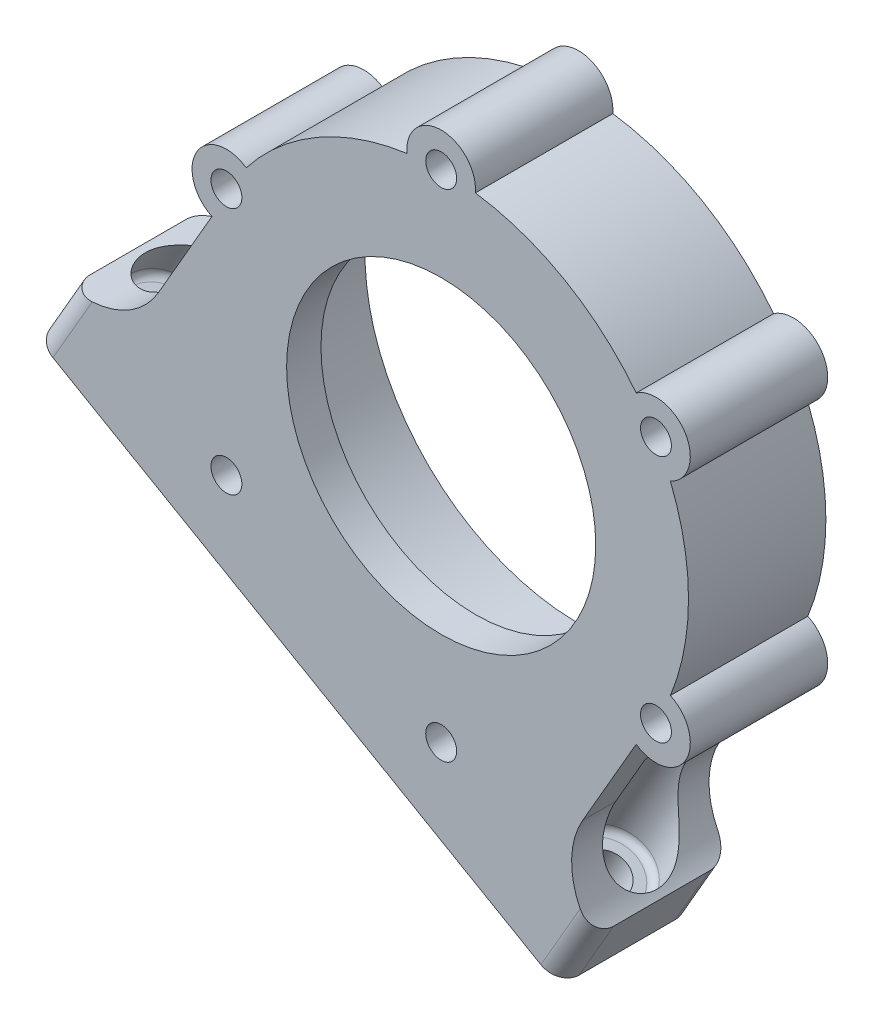
SolidWorks part; units mm, degrees
ref_plane "Front Plane" through (0, 0, 0) normal (0, 0, 1) x (1, 0, 0)
ref_plane "Top Plane" through (0, 0, 0) normal (0, 1, 0) x (1, 0, 0)
ref_plane "Right Plane" through (0, 0, 0) normal (1, 0, 0) x (0, 0, -1)
sketch "Sketch1" plane through (0, 0, 0) normal (0, 0, 1) x (1, 0, 0)
  circle A0 centre (0, 0) radius 31.1
  circle A1 centre (0, 0) radius 36
  dimension "D1" = 72
  dimension "D2" = 62.2
extrude "Boss-Extrude1" add sketch "Sketch1" along normal blind 15
sketch "Sketch2" plane through (0, 0, 15) normal (0, 0, 1) x (1, 0, 0)
  circle A0 centre (0, 0) radius 36
extrude "Boss-Extrude2" add sketch "Sketch2" along normal blind 5
sketch "Sketch3" plane through (0, 0, 20) normal (0, 0, 1) x (1, 0, 0)
  circle A0 centre (0, 0) radius 22.5
  dimension "D1" = 45
extrude "Cut-Extrude1" cut sketch "Sketch3" against normal blind 5
sketch "Sketch4" plane through (0, 0, 0) normal (0, 0, -1) x (-1, 0, 0)
  line L0 (0, 0) -> (0, 36) construction
  circle A0 centre (0, 0) radius 31.1 construction
  circle A1 centre (0, 36.1) radius 5
  circle A2 centre (31.2635, 18.05) radius 5
  circle A3 centre (31.2635, -18.05) radius 5
  circle A4 centre (0, -36.1) radius 5
  circle A5 centre (-31.2635, -18.05) radius 5
  circle A6 centre (-31.2635, 18.05) radius 5
  point P20 (0, 0)
  dimension "D1" = 10
  dimension "D2" = 6
extrude "Boss-Extrude3" add sketch "Sketch4" against normal up to surface (20 mm away) up to face at (22.5, 0, 20)
sketch "Sketch8" plane through (0, 0, 0) normal (0, 0, -1) x (-1, 0, 0)
  line L0 (-28.3871, -22.1398) -> (-9.8771, -54.2001)
  line L1 (-9.8771, -54.2001) -> (51.8772, -18.5462)
  line L2 (51.8772, -18.5462) -> (33.3672, 13.5141)
  line L3 (21, -36.3731) -> (0, 0) construction
  line L4 (-28.3871, -22.1398) -> (33.3672, 13.5141) construction
  arc A0 (-28.3871, -22.1398) -> (33.3672, 13.5141) centre (0, 0) ccw
  dimension "D1" = 37.02
extrude "Boss-Extrude4" add sketch "Sketch8" against normal blind 20
sketch "Sketch7" plane through (0, 0, 0) normal (0, 0, -1) x (-1, 0, 0)
  circle A0 centre (-31.2635, 18.05) radius 2.25
  circle A1 centre (0, 36.1) radius 2.25
  circle A2 centre (31.2635, 18.05) radius 2.25
  circle A3 centre (31.2635, -18.05) radius 2.25
  circle A4 centre (0, -36.1) radius 2.25
  circle A5 centre (-31.2635, -18.05) radius 2.25
  arc A6 (-28.3871, 22.1398) -> (-33.3672, 13.5141) centre (-31.2635, 18.05) ccw construction
  point P18 (0, 0)
  dimension "D1" = 4.5
  dimension "D2" = 6
extrude "Cut-Extrude2" cut sketch "Sketch7" against normal through all
sketch "Sketch9" plane through (-21, -36.3731, 0) normal (-0.5, -0.866, 0) x (0.866, -0.5, 0)
  line L0 (0, 0) -> (0, 15.6086) construction
  line L1 (-35.6539, 0) -> (-44.0039, 0)
  line L2 (-35.6539, 0) -> (-35.6539, 20)
  line L3 (-35.6539, 20) -> (-44.0039, 20)
  line L4 (-44.0039, 0) -> (-44.0039, 20)
  line L5 (35.6539, 0) -> (-35.6539, 0) construction
  line L6 (44.0039, 0) -> (44.0039, 20)
  line L7 (35.6539, 20) -> (44.0039, 20)
  line L8 (35.6539, 0) -> (35.6539, 20)
  line L9 (35.6539, 0) -> (44.0039, 0)
  dimension "D1" = 8.35
extrude "Boss-Extrude5" add sketch "Sketch9" against normal blind 10
fillet "Fillet1" radius 12 2 edges at (-46.8772, -9.8859, 10) (14.8771, -45.5398, 10)
sketch "Sketch10" plane through (-21, -36.3731, 0) normal (-0.5, -0.866, 0) x (0.866, -0.5, 0)
  line L0 (44.0039, 10) -> (0, 10) construction
  line L1 (44.0039, 0) -> (44.0039, 20) construction
  line L2 (0, 10) -> (0, 0) construction
  line L3 (44.0039, 0) -> (-44.0039, 0) construction
  circle A0 centre (37.5039, 10) radius 3
  circle A1 centre (-37.5039, 10) radius 3
  circle A2 centre (37.5039, 10) radius 5.5
  circle A3 centre (-37.5039, 10) radius 5.5
  dimension "D1" = 6
  dimension "D3" = 6.5
  dimension "D2" = 11
extrude "Cut-Extrude3" cut sketch "Sketch10" against normal blind 30 contours A0 | A1 region at (11.4793, -55.1251, 10) region at (-53.4793, -17.6212, 10)
extrude "Cut-Extrude5" cut sketch "Sketch10<4>" against normal blind 25 from offset 5 offset against normal yes
sketch "Sketch10<4>" plane through (-21, -36.3731, 0) normal (-0.5, -0.866, 0) x (0.866, -0.5, 0) same geometry as "Sketch10"
fillet "Fillet2" radius 3 4 edges at (-56.6085, -10.0411, 20) (-56.6085, -10.0411, 0) (19.6084, -54.0449, 0) (19.6084, -54.0449, 20)
fillet "Fillet3" radius 1 2 edges at (18.7424, -53.5449, 10) (-55.7425, -10.5411, 10)
